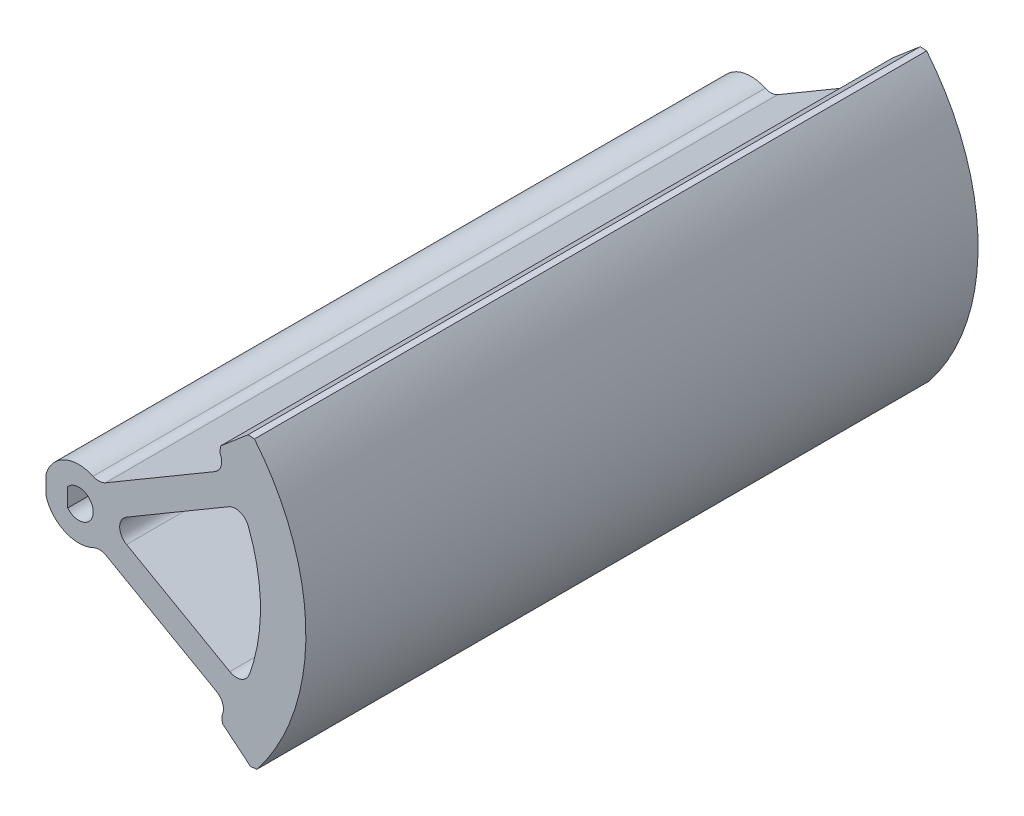
SolidWorks part; units mm, degrees
ref_plane "Front Plane" through (0, 0, 0) normal (0, 0, 1) x (1, 0, 0)
ref_plane "Top Plane" through (0, 0, 0) normal (0, 1, 0) x (1, 0, 0)
ref_plane "Right Plane" through (0, 0, 0) normal (1, 0, 0) x (0, 0, -1)
sketch "Sketch1" plane through (0, 0, 0) normal (0, 0, 1) x (1, 0, 0)
  line L0 (63.4381, 57.8516) -> (25.4, 25.4) construction
  line L1 (25.4, 25.4) -> (44.7929, 36.809) construction
  line L2 (55.8305, 51.3613) -> (63.4381, 57.8516)
  line L3 (31.3998, 25.4491) -> (61.3004, 43.0398)
  line L4 (25.4, 25.4) -> (57.7713, 25.6648) construction
  line L5 (29.8034, 31.4712) -> (58.258, 48.2112)
  line L6 (26.9212, 22.8143) -> (46.3141, 34.2233) construction
  line L7 (23.8788, 27.9857) -> (43.2717, 39.3947) construction
  line L8 (25.4, 25.4) -> (17.3828, 25.4) construction
  line L10 (26.4, 25.4082) -> (31.3998, 25.4491)
  line L11 (65.3987, 25.7271) -> (75.3983, 25.8089)
  line L12 (24.4464, 25.0988) -> (18.2482, 23.1413)
  arc A0 (26.4, 25.4082) -> (24.4, 25.4) centre (25.4, 25.4) ccw
  arc A1 (29.8034, 31.4712) -> (17.9, 25.4) centre (25.4, 25.4) ccw
  arc A2 (75.3983, 25.8089) -> (63.4381, 57.8516) centre (25.4, 25.4) ccw
  arc A3 (55.8305, 51.3613) -> (58.258, 48.2112) centre (25.4, 25.4) cw
  arc A4 (61.3004, 43.0398) -> (65.3987, 25.7271) centre (25.4, 25.4) cw
  arc A5 (24.4, 25.4) -> (24.4464, 25.0988) centre (25.4, 25.4) ccw
  arc A6 (17.9, 25.4) -> (18.2482, 23.1413) centre (25.4, 25.4) ccw
  dimension "D2" = 2
  dimension "D1" = 15
  dimension "D5" = 40
  dimension "D3" = 50
  dimension "D4" = 40
  dimension "D6" = 30
  dimension "D7" = 3
  dimension "D8" = 3
extrude "Boss-Extrude1" add sketch "Sketch1" against normal mid plane 148
ref_plane "Plane1" through (-0.206, 25.1906, 0) normal (0.0082, -1, 0) x (-1, -0.0082, 0)
mirror "Mirror1" about plane through (-0.206, 25.1906, 0) normal (0.0082, -1, 0) of "Boss-Extrude1"
chamfer "Chamfer1" distance 1 angle 45 4 edges at (55.8305, 51.3613, 0) (56.251, -0.06, 0) (63.4381, 57.8516, 0) (63.9638, -6.425, 0)
fillet "Fillet1" radius 3 7 edges at (58.6267, 3.1293, 0) (58.258, 48.2112, 0) (31.3998, 25.4491, 0) (61.5841, 8.3498, 0) (61.3004, 43.0398, 0) (29.9021, 19.4016, 0) (29.8034, 31.4712, 0)
sketch "Sketch3" plane through (0, 0, 0) normal (0, 0, 1) x (1, 0, 0)
  line L0 (22.9604, 23.368) -> (22.9604, 27.432)
  line L3 (18.1805, 27.432) -> (18.1805, 23.368)
  arc A0 (22.9604, 23.368) -> (22.9604, 27.432) centre (25.4, 25.4) ccw
  arc A1 (18.1805, 27.432) -> (18.1805, 23.368) centre (25.4, 25.4) ccw
  dimension "D1" = 6.35
  dimension "D2" = 4.064
extrude "Cut-Extrude1" cut sketch "Sketch3" against normal through all both and the other way through all
sketch "Sketch4" plane through (18.1805, 0, 0) normal (-1, 0, 0) x (0, 0, 1)
  line L0 (-74, 27.432) -> (74, 27.432) construction
  line L1 (0, 23.368) -> (0, 27.432) construction
  line L2 (-74, 23.368) -> (74, 23.368) construction
  circle A0 centre (0, 25.4) radius 1
  circle A1 centre (30, 25.4) radius 1
  circle A2 centre (60, 25.4) radius 1
  circle A3 centre (-30, 25.4) radius 1
  circle A4 centre (-60, 25.4) radius 1
  dimension "D1" = 2
  dimension "D2" = 3
  dimension "D3" = 3
extrude "Cut-Extrude2" cut sketch "Sketch4" against normal up to next
